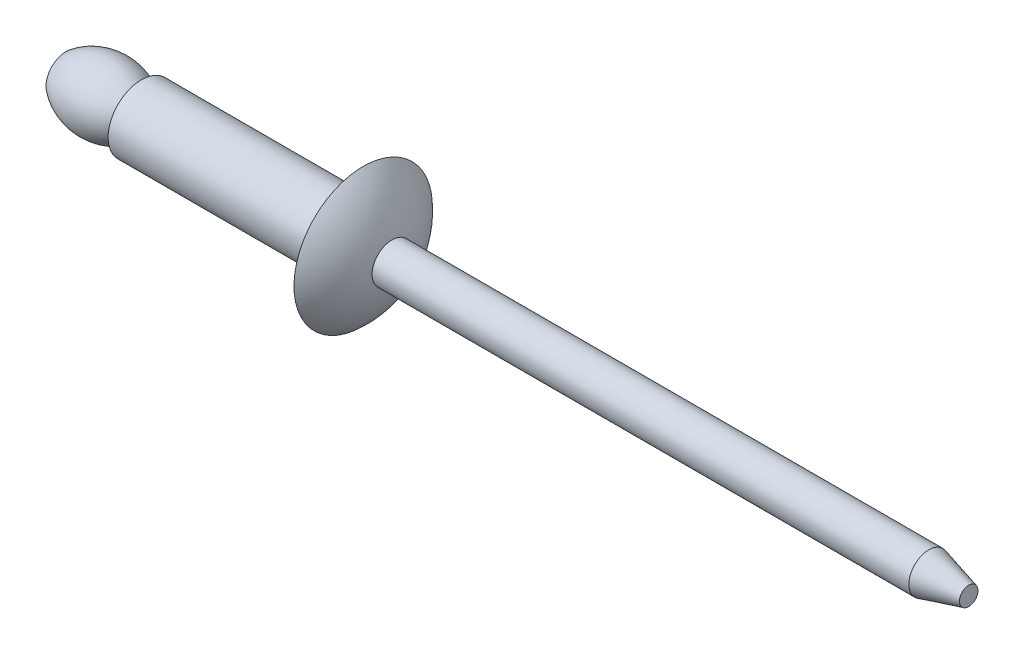
SolidWorks part; units mm, degrees
ref_plane "Front" through (0, 0, 0) normal (0, 0, 1) x (1, 0, 0)
ref_plane "Top" through (0, 0, 0) normal (0, 1, 0) x (1, 0, 0)
ref_plane "Right" through (0, 0, 0) normal (1, 0, 0) x (0, 0, -1)
sketch "Sketch1" plane through (-11.6035, 14.7235, 0) normal (0, 0, 1) x (0, -1, 0)
  line L0 (15.6235, 15.0035) -> (16.2235, 15.0035)
  line L1 (16.2235, 15.0035) -> (16.2235, 25.0035)
  line L2 (16.2235, 25.0035) -> (17.8435, 25.0035)
  line L3 (14.7235, 34.3377) -> (14.7235, -10.975) construction
  line L4 (15.6235, 26.3053) -> (15.6235, 52.3053)
  line L5 (15.6235, 52.3053) -> (14.7235, 52.3053)
  line L6 (14.7235, 11.6035) -> (14.7235, 52.3053)
  line L7 (15.6235, 11.6035) -> (14.7235, 11.6035)
  arc A0 (17.8435, 25.0035) -> (15.6235, 26.3053) centre (14.7235, 22.2269) ccw
  arc A1 (15.6235, 15.0035) -> (15.6235, 11.6035) centre (13.5151, 13.3035) cw
revolve "Base-Revolve" add sketch "Sketch1" angle 360 about L3
fillet "Fillet1" radius 0.5 1 edges at (13.4, 1.5, 0)
chamfer "Chamfer1" distance 1.8 angle 15 1 edges at (40.7019, 0.9, 0) first distance on face at (40.7019, 0.9, 0)
equation "\"D1@Chamfer1\" = \"d1@Sketch1\""
